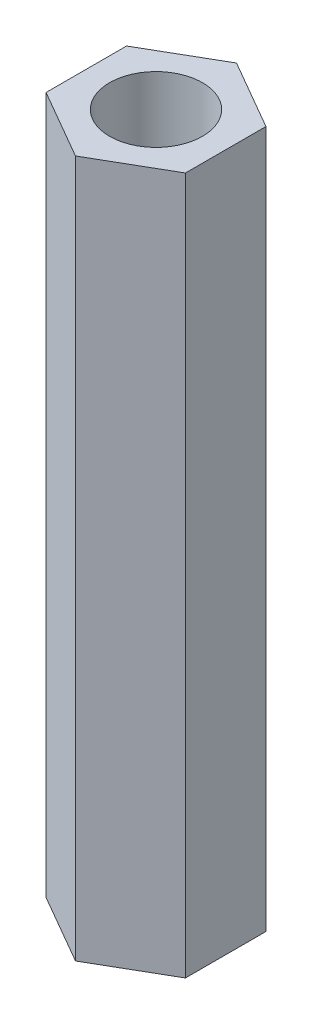
SolidWorks part; units mm, degrees
ref_plane "Front Plane" through (0, 0, 0) normal (0, 0, 1) x (1, 0, 0)
ref_plane "Top Plane" through (0, 0, 0) normal (0, 1, 0) x (1, 0, 0)
ref_plane "Right Plane" through (0, 0, 0) normal (1, 0, 0) x (0, 0, -1)
sketch "Sketch1" plane through (0, 0, 0) normal (0, 1, 0) x (1, 0, 0)
  line L1 (0, -1.7321) -> (1.5, -0.866)
  line L2 (1.5, -0.866) -> (1.5, 0.866)
  line L3 (1.5, 0.866) -> (0, 1.7321)
  line L4 (0, 1.7321) -> (-1.5, 0.866)
  line L5 (-1.5, 0.866) -> (-1.5, -0.866)
  line L6 (-1.5, -0.866) -> (0, -1.7321)
  circle A0 centre (0, 0) radius 1.5 construction
  circle A1 centre (0, 0) radius 1
  dimension "D2" = 2
  dimension "D1" = 3
extrude "Boss-Extrude1" add sketch "Sketch1" along normal blind 15
